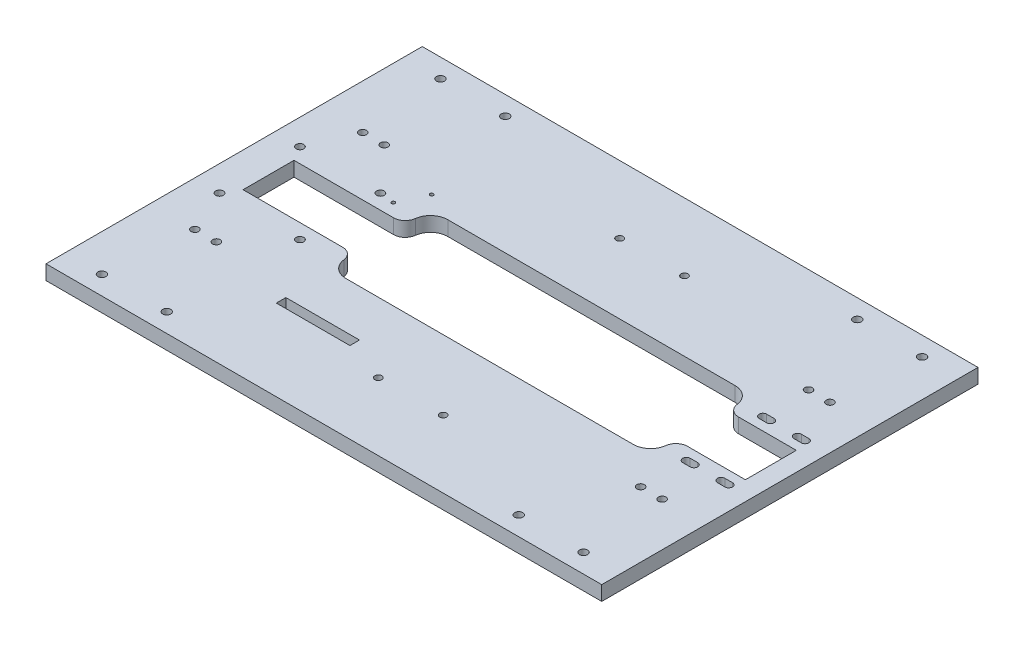
SolidWorks part; units mm, degrees
ref_plane "Front Plane" through (0, 0, 0) normal (0, 0, 1) x (1, 0, 0)
ref_plane "Top Plane" through (0, 0, 0) normal (0, 1, 0) x (1, 0, 0)
ref_plane "Right Plane" through (0, 0, 0) normal (1, 0, 0) x (0, 0, -1)
sketch "Sketch1" plane through (0, 0, 0) normal (0, 1, 0) x (1, 0, 0)
  line L1 (-240, 162.5) -> (240, 162.5)
  line L2 (-240, 162.5) -> (-240, -162.5)
  line L3 (-240, -162.5) -> (240, -162.5)
  line L4 (240, 162.5) -> (240, -162.5)
  line L5 (-240, 162.5) -> (240, -162.5) construction
  line L6 (-240, -162.5) -> (240, 162.5) construction
  point P0 (0, 0)
  dimension "D1" = 480
  dimension "D2" = 325
extrude "Boss-Extrude1" add sketch "Sketch1" along normal blind 12.6
sketch "Sketch2" plane through (0, 0, 0) normal (0, -1, 0) x (1, 0, 0)
  circle A0 centre (44.7486, -104.2) radius 3
  circle A1 centre (-11.2514, -104.2) radius 3
  circle A2 centre (44.7486, 104.2) radius 3
  circle A3 centre (-11.2514, 104.2) radius 3
extrude "Cut-Extrude1" cut sketch "Sketch2" against normal up to next
sketch "Sketch3" plane through (0, 0, 0) normal (0, -1, 0) x (1, 0, 0)
  line L0 (-192.4406, 0) -> (188.5847, 0) construction
  line L1 (163.5847, 44) -> (-114.2887, 44)
  line L2 (163.5847, 44) -> (163.5847, 22)
  line L3 (163.5847, -44) -> (-114.2887, -44)
  line L5 (-114.2887, -44) -> (-114.2887, -22)
  line L6 (-114.2887, -22) -> (-210.2887, -22)
  line L7 (-114.2887, 44) -> (-114.2887, 22)
  line L8 (-114.2887, 22) -> (-210.2887, 22)
  line L9 (-210.2887, 22) -> (-210.2887, -22)
  line L10 (163.5847, 22) -> (223.5847, 22)
  line L11 (223.5847, 22) -> (223.5847, -22)
  line L12 (223.5847, -22) -> (163.5847, -22)
  line L13 (163.5847, -22) -> (163.5847, -44)
  point P0 (0, 0)
  point P1 (-210.2887, 0)
  dimension "D2" = 96
  dimension "D1" = 22
  dimension "D5" = 60
extrude "Cut-Extrude2" cut sketch "Sketch3" against normal up to next
fillet "Fillet1" radius 10 2 edges at (-114.2887, 6.3, 22) (-114.2887, 6.3, -22)
sketch "Sketch4" plane through (0, 0, 0) normal (0, -1, 0) x (1, 0, 0)
  circle A12 centre (-148.4257, -34.75) radius 3.3
  circle A13 centre (-148.4257, 34.75) radius 3.3
  circle A14 centre (-217.9257, 34.75) radius 3.3
  circle A15 centre (-217.9257, -34.75) radius 3.3
extrude "Cut-Extrude3" cut sketch "Sketch4" against normal up to next
fillet "Fillet2" radius 10 2 edges at (163.5847, 6.3, -22) (163.5847, 6.3, 22)
sketch "Sketch7" plane through (0, 12.6, 0) normal (0, 1, 0) x (1, 0, 0)
  circle A0 centre (208, -146.2) radius 2.25
  circle A1 centre (152, -146.2) radius 2.25
  circle A2 centre (-152, -146.2) radius 2.25
  circle A3 centre (-208, -146.2) radius 2.25
  circle A4 centre (-208, 146.2) radius 2.25
  circle A5 centre (-152, 146.2) radius 2.25
  circle A6 centre (208, 146.2) radius 2.25
  circle A7 centre (152, 146.2) radius 2.25
  dimension "D1" = 4.5
extrude "Cut-Extrude7" cut sketch "Sketch7" against normal up to next
sketch "Sketch8" plane through (0, 12.6, 0) normal (0, 1, 0) x (1, 0, 0)
  circle A0 centre (208, 146.2) radius 3.5
  circle A1 centre (152, 146.2) radius 3.5
  circle A2 centre (-152, 146.2) radius 3.5
  circle A3 centre (-208, 146.2) radius 3.5
  circle A4 centre (208, -146.2) radius 3.5
  circle A5 centre (152, -146.2) radius 3.5
  circle A6 centre (-208, -146.2) radius 3.5
  circle A7 centre (-152, -146.2) radius 3.5
  dimension "D1" = 7
extrude "Cut-Extrude8" cut sketch "Sketch8" against normal blind 6
sketch "Sketch12" plane through (0, 0, 0) normal (0, -1, 0) x (1, 0, 0)
  circle A0 centre (-135.8148, -33.2631) radius 1.5
  circle A1 centre (-125.2148, -55.8631) radius 1.5
extrude "Cut-Extrude11" cut sketch "Sketch12" against normal up to next
fillet "Fillet3" radius 15 4 edges at (163.5847, 6.3, 44) (163.5847, 6.3, -44) (-114.2887, 6.3, 44) (-114.2887, 6.3, -44)
sketch "Sketch14" plane through (0, 12.6, 0) normal (0, 1, 0) x (1, 0, 0)
  line L1 (-111.1572, -84.1633) -> (-47.573, -84.1633)
  line L2 (-111.1572, -84.1633) -> (-111.1572, -92.4204)
  line L3 (-111.1572, -92.4204) -> (-47.573, -92.4204)
  line L4 (-47.573, -84.1633) -> (-47.573, -92.4204)
extrude "Cut-Extrude13" cut sketch "Sketch14" against normal through all
sketch "Sketch15" plane through (0, 12.6, 0) normal (0, 1, 0) x (1, 0, 0)
  line L0 (-201.3752, -109.7364) -> (-201.3752, 118.5225) construction
  line L1 (-182.8647, -109.7364) -> (-182.8647, 113.1876) construction
  line L2 (-257.879, -72.5) -> (-138.224, -72.5) construction
  line L3 (-257.879, 72.5) -> (-138.224, 72.5) construction
  line L4 (183.6248, -104.4043) -> (183.6248, 127.2576) construction
  line L5 (202.1353, -104.4043) -> (202.1353, 113.1876) construction
  line L6 (152.11, 72.5) -> (276.9157, 72.5) construction
  line L7 (152.11, -72.5) -> (265.9977, -72.5) construction
  circle A8 centre (-201.3752, -72.5) radius 3.25
  circle A9 centre (-182.8647, -72.5) radius 3.25
  circle A10 centre (-201.3752, 72.5) radius 3.25
  circle A11 centre (-182.8647, 72.5) radius 3.25
  circle A12 centre (183.6248, 72.5) radius 3.25
  circle A13 centre (202.1353, 72.5) radius 3.25
  circle A14 centre (183.6248, -72.5) radius 3.25
  circle A15 centre (202.1353, -72.5) radius 3.25
  point P32 (183.6248, 72.5)
  point P33 (202.1353, 72.5)
extrude "Cut-Extrude14" cut sketch "Sketch15" against normal up to next
sketch "Sketch16" plane through (0, 12.6, 0) normal (0, 1, 0) x (1, 0, 0)
  line L0 (183.6729, -33) -> (186.9229, -33) construction
  line L1 (213.6729, -33) -> (216.9229, -33) construction
  line L2 (183.6729, 33) -> (186.9229, 33) construction
  line L3 (213.6729, 33) -> (216.9229, 33) construction
  line L4 (183.6729, -36.25) -> (190.1729, -36.25)
  line L5 (183.6729, -29.75) -> (190.1729, -29.75)
  line L6 (213.6729, -36.25) -> (220.1729, -36.25)
  line L7 (213.6729, -29.75) -> (220.1729, -29.75)
  line L8 (183.6729, 29.75) -> (190.1729, 29.75)
  line L9 (183.6729, 36.25) -> (190.1729, 36.25)
  line L10 (213.6729, 29.75) -> (220.1729, 29.75)
  line L11 (213.6729, 36.25) -> (220.1729, 36.25)
  arc A4 (213.6729, -29.75) -> (213.6729, -36.25) centre (213.6729, -33) ccw
  arc A5 (183.6729, -29.75) -> (183.6729, -36.25) centre (183.6729, -33) ccw
  arc A6 (183.6729, 36.25) -> (183.6729, 29.75) centre (183.6729, 33) ccw
  arc A7 (213.6729, 36.25) -> (213.6729, 29.75) centre (213.6729, 33) ccw
  arc A8 (190.1729, -36.25) -> (190.1729, -29.75) centre (190.1729, -33) ccw
  arc A9 (220.1729, -36.25) -> (220.1729, -29.75) centre (220.1729, -33) ccw
  arc A10 (220.1729, 29.75) -> (220.1729, 36.25) centre (220.1729, 33) ccw
  arc A11 (190.1729, 29.75) -> (190.1729, 36.25) centre (190.1729, 33) ccw
  dimension "D1" = 6.5
  dimension "D2" = 6.5
  dimension "D3" = 6.5
  dimension "D4" = 6.5
extrude "Cut-Extrude15" cut sketch "Sketch16" against normal up to next
sketch "Sketch17" plane through (0, 0, 0) normal (0, 1, 0) x (1, 0, 0)
  line L0 (-47.573, -92.4204) -> (-47.573, -84.1633) construction
  line L1 (-111.1572, -92.4204) -> (-47.573, -92.4204) construction
  line L2 (-111.1572, -84.1633) -> (-111.1572, -92.4204) construction
  line L3 (-47.573, -84.1633) -> (-111.1572, -84.1633) construction
  line L4 (240, -162.5) -> (240, 162.5)
  line L5 (240, 162.5) -> (-240, 162.5)
  line L6 (-240, 162.5) -> (-240, -162.5)
  line L7 (-240, -162.5) -> (240, -162.5)
  line L8 (240, -162.5) -> (240, 162.5)
  line L9 (240, 162.5) -> (-240, 162.5)
  line L10 (-240, 162.5) -> (-240, -162.5)
  line L11 (-240, -162.5) -> (240, -162.5)
  line L12 (-47.573, -92.4204) -> (-47.573, -84.1633)
  line L13 (-111.1572, -92.4204) -> (-47.573, -92.4204)
  line L14 (-111.1572, -84.1633) -> (-111.1572, -92.4204)
  line L15 (-47.573, -84.1633) -> (-111.1572, -84.1633)
  line L22 (220.1729, 36.25) -> (213.6729, 36.25)
  line L23 (213.6729, 29.75) -> (220.1729, 29.75)
  line L24 (148.7654, 44) -> (-99.4693, 44)
  line L25 (223.5847, 22) -> (173.5847, 22)
  line L26 (223.5847, -22) -> (223.5847, 22)
  line L27 (173.5847, -22) -> (223.5847, -22)
  line L28 (-99.4693, -44) -> (148.7654, -44)
  line L29 (-210.2887, -22) -> (-124.2887, -22)
  line L30 (-210.2887, 22) -> (-210.2887, -22)
  line L31 (-124.2887, 22) -> (-210.2887, 22)
  line L32 (148.7654, 44) -> (-99.4693, 44)
  line L33 (223.5847, 22) -> (173.5847, 22)
  line L34 (223.5847, -22) -> (223.5847, 22)
  line L35 (173.5847, -22) -> (223.5847, -22)
  line L36 (-99.4693, -44) -> (148.7654, -44)
  line L37 (-210.2887, -22) -> (-124.2887, -22)
  line L38 (-210.2887, 22) -> (-210.2887, -22)
  line L39 (-124.2887, 22) -> (-210.2887, 22)
  line L40 (220.1729, 36.25) -> (213.6729, 36.25)
  line L41 (213.6729, 29.75) -> (220.1729, 29.75)
  line L42 (190.1729, 36.25) -> (183.6729, 36.25)
  line L43 (183.6729, 29.75) -> (190.1729, 29.75)
  line L44 (190.1729, 36.25) -> (183.6729, 36.25)
  line L45 (183.6729, 29.75) -> (190.1729, 29.75)
  line L46 (220.1729, -29.75) -> (213.6729, -29.75)
  line L47 (213.6729, -36.25) -> (220.1729, -36.25)
  line L48 (220.1729, -29.75) -> (213.6729, -29.75)
  line L49 (213.6729, -36.25) -> (220.1729, -36.25)
  line L50 (190.1729, -29.75) -> (183.6729, -29.75)
  line L51 (183.6729, -36.25) -> (190.1729, -36.25)
  line L52 (190.1729, -29.75) -> (183.6729, -29.75)
  line L53 (183.6729, -36.25) -> (190.1729, -36.25)
  circle A0 centre (44.7486, -104.2) radius 3 construction
  circle A1 centre (-11.2514, -104.2) radius 3 construction
  circle A2 centre (208, -146.2) radius 2.25 construction
  circle A3 centre (152, -146.2) radius 2.25 construction
  circle A4 centre (202.1353, -72.5) radius 3.25 construction
  circle A5 centre (183.6248, -72.5) radius 3.25 construction
  circle A6 centre (202.1353, 72.5) radius 3.25 construction
  circle A7 centre (183.6248, 72.5) radius 3.25 construction
  circle A8 centre (208, 146.2) radius 2.25 construction
  circle A9 centre (152, 146.2) radius 2.25 construction
  circle A10 centre (44.7486, 104.2) radius 3 construction
  circle A11 centre (-11.2514, 104.2) radius 3 construction
  circle A12 centre (-125.2148, 55.8631) radius 1.5 construction
  circle A13 centre (-135.8148, 33.2631) radius 1.5 construction
  circle A14 centre (-148.4257, 34.75) radius 3.3 construction
  circle A15 centre (-217.9257, 34.75) radius 3.3 construction
  circle A16 centre (-182.8647, 72.5) radius 3.25 construction
  circle A17 centre (-201.3752, 72.5) radius 3.25 construction
  circle A18 centre (-152, 146.2) radius 2.25 construction
  circle A19 centre (-208, 146.2) radius 2.25 construction
  circle A20 centre (-217.9257, -34.75) radius 3.3 construction
  circle A21 centre (-148.4257, -34.75) radius 3.3 construction
  circle A22 centre (-182.8647, -72.5) radius 3.25 construction
  circle A23 centre (-201.3752, -72.5) radius 3.25 construction
  circle A24 centre (-152, -146.2) radius 2.25 construction
  circle A25 centre (-208, -146.2) radius 2.25 construction
  circle A26 centre (44.7486, -104.2) radius 3
  circle A27 centre (-11.2514, -104.2) radius 3
  circle A28 centre (208, -146.2) radius 2.25
  circle A29 centre (152, -146.2) radius 2.25
  circle A30 centre (202.1353, -72.5) radius 3.25
  circle A31 centre (183.6248, -72.5) radius 3.25
  circle A32 centre (202.1353, 72.5) radius 3.25
  circle A33 centre (183.6248, 72.5) radius 3.25
  circle A34 centre (208, 146.2) radius 2.25
  circle A35 centre (152, 146.2) radius 2.25
  circle A36 centre (44.7486, 104.2) radius 3
  circle A37 centre (-11.2514, 104.2) radius 3
  circle A38 centre (-125.2148, 55.8631) radius 1.5
  circle A39 centre (-135.8148, 33.2631) radius 1.5
  circle A40 centre (-148.4257, 34.75) radius 3.3
  circle A41 centre (-217.9257, 34.75) radius 3.3
  circle A42 centre (-182.8647, 72.5) radius 3.25
  circle A43 centre (-201.3752, 72.5) radius 3.25
  circle A44 centre (-152, 146.2) radius 2.25
  circle A45 centre (-208, 146.2) radius 2.25
  circle A46 centre (-217.9257, -34.75) radius 3.3
  circle A47 centre (-148.4257, -34.75) radius 3.3
  circle A48 centre (-182.8647, -72.5) radius 3.25
  circle A49 centre (-201.3752, -72.5) radius 3.25
  circle A50 centre (-152, -146.2) radius 2.25
  circle A51 centre (-208, -146.2) radius 2.25
  arc A54 (213.6729, 36.25) -> (213.6729, 29.75) centre (213.6729, 33) ccw
  arc A55 (220.1729, 29.75) -> (220.1729, 36.25) centre (220.1729, 33) ccw
  arc A56 (213.6729, 36.25) -> (213.6729, 29.75) centre (213.6729, 33) ccw
  arc A57 (220.1729, 29.75) -> (220.1729, 36.25) centre (220.1729, 33) ccw
  arc A58 (183.6729, 36.25) -> (183.6729, 29.75) centre (183.6729, 33) ccw
  arc A59 (190.1729, 29.75) -> (190.1729, 36.25) centre (190.1729, 33) ccw
  arc A60 (163.657, 30.8) -> (148.7654, 44) centre (148.7654, 29) ccw
  arc A61 (163.657, 30.8) -> (173.5847, 22) centre (173.5847, 32) ccw
  arc A62 (173.5847, -22) -> (163.657, -30.8) centre (173.5847, -32) ccw
  arc A63 (148.7654, -44) -> (163.657, -30.8) centre (148.7654, -29) ccw
  arc A64 (-114.3609, -30.8) -> (-99.4693, -44) centre (-99.4693, -29) ccw
  arc A65 (-114.3609, -30.8) -> (-124.2887, -22) centre (-124.2887, -32) ccw
  arc A66 (-124.2887, 22) -> (-114.3609, 30.8) centre (-124.2887, 32) ccw
  arc A67 (-99.4693, 44) -> (-114.3609, 30.8) centre (-99.4693, 29) ccw
  arc A68 (163.657, 30.8) -> (148.7654, 44) centre (148.7654, 29) ccw
  arc A69 (163.657, 30.8) -> (173.5847, 22) centre (173.5847, 32) ccw
  arc A70 (173.5847, -22) -> (163.657, -30.8) centre (173.5847, -32) ccw
  arc A71 (148.7654, -44) -> (163.657, -30.8) centre (148.7654, -29) ccw
  arc A72 (-114.3609, -30.8) -> (-99.4693, -44) centre (-99.4693, -29) ccw
  arc A73 (-114.3609, -30.8) -> (-124.2887, -22) centre (-124.2887, -32) ccw
  arc A74 (-124.2887, 22) -> (-114.3609, 30.8) centre (-124.2887, 32) ccw
  arc A75 (-99.4693, 44) -> (-114.3609, 30.8) centre (-99.4693, 29) ccw
  arc A76 (183.6729, 36.25) -> (183.6729, 29.75) centre (183.6729, 33) ccw
  arc A77 (190.1729, 29.75) -> (190.1729, 36.25) centre (190.1729, 33) ccw
  arc A78 (213.6729, -29.75) -> (213.6729, -36.25) centre (213.6729, -33) ccw
  arc A79 (220.1729, -36.25) -> (220.1729, -29.75) centre (220.1729, -33) ccw
  arc A80 (213.6729, -29.75) -> (213.6729, -36.25) centre (213.6729, -33) ccw
  arc A81 (220.1729, -36.25) -> (220.1729, -29.75) centre (220.1729, -33) ccw
  arc A82 (183.6729, -29.75) -> (183.6729, -36.25) centre (183.6729, -33) ccw
  arc A83 (190.1729, -36.25) -> (190.1729, -29.75) centre (190.1729, -33) ccw
  arc A84 (183.6729, -29.75) -> (183.6729, -36.25) centre (183.6729, -33) ccw
  arc A85 (190.1729, -36.25) -> (190.1729, -29.75) centre (190.1729, -33) ccw
  dimension "D1" = 0
  dimension "D2" = 0
  dimension "D3" = 0
  dimension "D4" = 0
  dimension "D5" = 0
  dimension "D6" = 0
